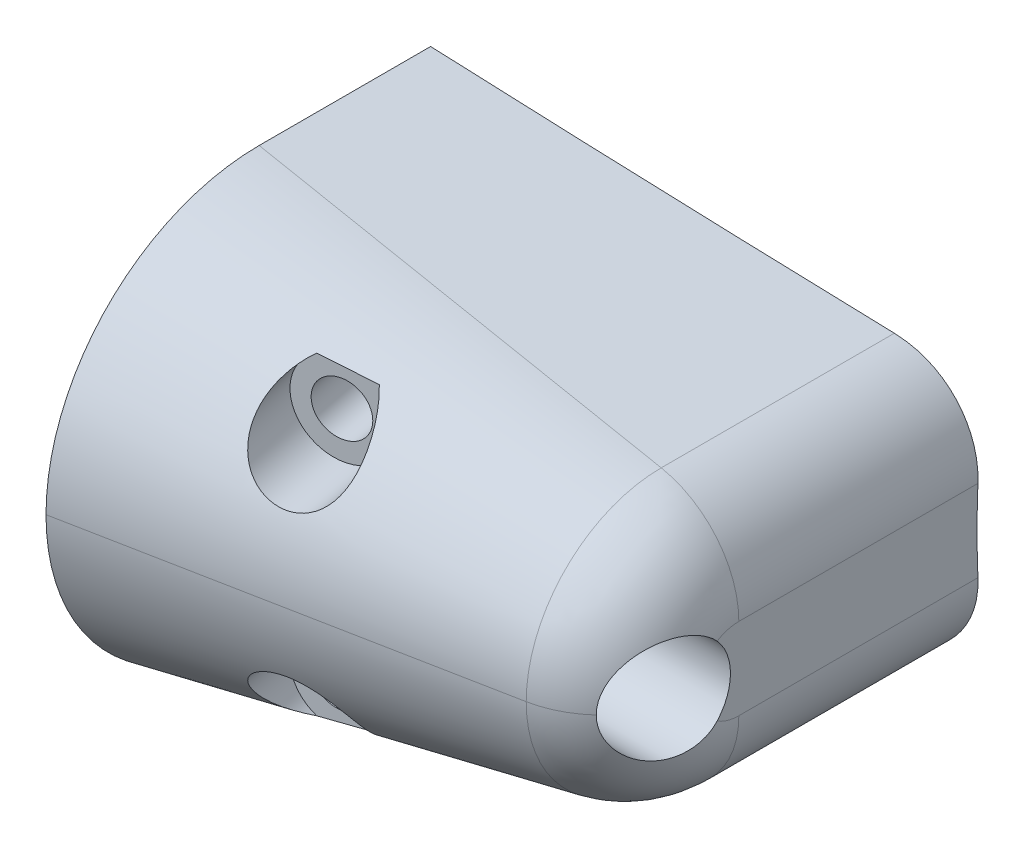
SolidWorks part; units mm, degrees
ref_plane "Plan de face" through (0, 0, 0) normal (0, 0, 1) x (1, 0, 0)
ref_plane "Plan de dessus" through (0, 0, 0) normal (0, 1, 0) x (1, 0, 0)
ref_plane "Plan de droite" through (0, 0, 0) normal (1, 0, 0) x (0, 0, -1)
sketch "Esquisse1" plane through (0, 0, 0) normal (0, 0, 1) x (1, 0, 0)
  line L1 (0, -6) -> (20, -6)
  line L2 (0, -6) -> (0, 12)
  line L3 (0, 12) -> (20, 12)
  line L4 (20, -6) -> (20, 12)
  dimension "D1" = 20
  dimension "D2" = 18
extrude "Boss.-Extru.1" add sketch "Esquisse1" along normal blind 20
sketch "Esquisse2" plane through (0, 12, 0) normal (0, 1, 0) x (1, 0, 0)
  line L0 (20.0456, -0.0409) -> (0, -3.849)
  line L1 (0, -20) -> (0, 0) construction
  line L2 (0, -3.849) -> (0, 0)
extrude "Enlèv. mat.-Extru.1" cut sketch "Esquisse2" against normal through all and the other way through all flip side to cut
sketch "Esquisse4" plane through (0.7057, 0, 3.715) normal (-0.1866, 0, -0.9824) x (-0.9824, 0, 0.1866)
  line L0 (-19.6393, -6) -> (-19.6393, 12) construction
  line L1 (-19.6393, 11.9) -> (3.7327, 11.9)
  line L2 (-19.6393, 11.9) -> (-19.6393, -5.9)
  line L3 (-19.6393, -5.9) -> (3.7327, -5.9)
  line L4 (3.7327, 11.9) -> (3.7327, -5.9)
  line L6 (-19.6393, 12) -> (0.7184, 12) construction
  line L7 (0.7184, -6) -> (-19.6393, -6) construction
  line L8 (3.7327, 12) -> (3.7327, -6) construction
  dimension "D1" = 0
  dimension "D2" = 0
  dimension "D3" = 0.1
  dimension "D4" = 0.1
extrude "Enlèv. mat.-Extru.3" cut sketch "Esquisse4" against normal blind 1
ref_plane "Plan2" through (4.3638, 0, 22.9705) normal (-0.1866, 0, -0.9824) x (-0.9824, 0, 0.1866)
fillet "Congé2" radius 40 2 edges at (10, 11.9, 2.9672) (10, -5.9, 2.9672)
sketch "Esquisse5" plane through (0, 0, 0) normal (-1, 0, 0) x (0, 0, 1)
  line L0 (20, 12) -> (3.849, 12) construction
  line L1 (20, -6) -> (3.849, -6) construction
  line L2 (20, 12) -> (20, -6) construction
  circle A0 centre (13.5, 3) radius 2.15
  dimension "D1" = 9
  dimension "D2" = 9
  dimension "D3" = 6.5
extrude "Enlèv. mat.-Extru.4" cut sketch "Esquisse5" against normal through all
fillet "Congé3" radius 9 2 edges at (10, 12, 20) (10, -6, 20)
chamfer "Chanfrein1" distance 4 angle 79 4 edges at (20, -6, 5.5248) (20, -3.364, 17.364) (20, 9.364, 17.364) (20, 12, 5.5248)
fillet "Congé4" radius 4 4 edges at (20, -2, 5.8748) (20, -0.5355, 14.5355) (20, 6.5355, 14.5355) (20, 8, 5.8748)
sketch "Esquisse6" plane through (248.3542, 0, -23.3813) normal (-0.1866, 0, -0.9824) x (-0.9824, 0, 0.1866)
  circle A0 centre (244, 7.9) radius 1.1
  circle A1 centre (244, -1.9) radius 1.1
  point P2 (0, 0)
  point P3 (0, 0)
  point P6 (0, 0)
  point P7 (0, 0)
  point P8 (0, 0)
  point P9 (0, 0)
  point P10 (0, 0)
  point P11 (0, 0)
  point P12 (0, 0)
  point P13 (0, 0)
  point P14 (0, 0)
  point P15 (0, 0)
  point P16 (0, 0)
  point P17 (0, 0)
  point P18 (0, 0)
  point P19 (0, 0)
  point P20 (0, 0)
extrude "Enlèv. mat.-Extru.5" cut sketch "Esquisse6" along normal through all
sketch "Esquisse10" plane through (4.3638, 0, 22.9705) normal (-0.1866, 0, -0.9824) x (-0.9824, 0, 0.1866)
  circle A0 centre (-4.4, 7.9) radius 1.9
  circle A1 centre (-4.4, -1.9) radius 1.9
  point P4 (0, 0)
  point P5 (0, 0)
  point P6 (0, 0)
  point P7 (0, 0)
  point P8 (0, 0)
  point P9 (0, 0)
  point P10 (0, 0)
  point P11 (0, 0)
extrude "Enlèv. mat.-Extru.6" cut sketch "Esquisse10" along normal blind 7.5
